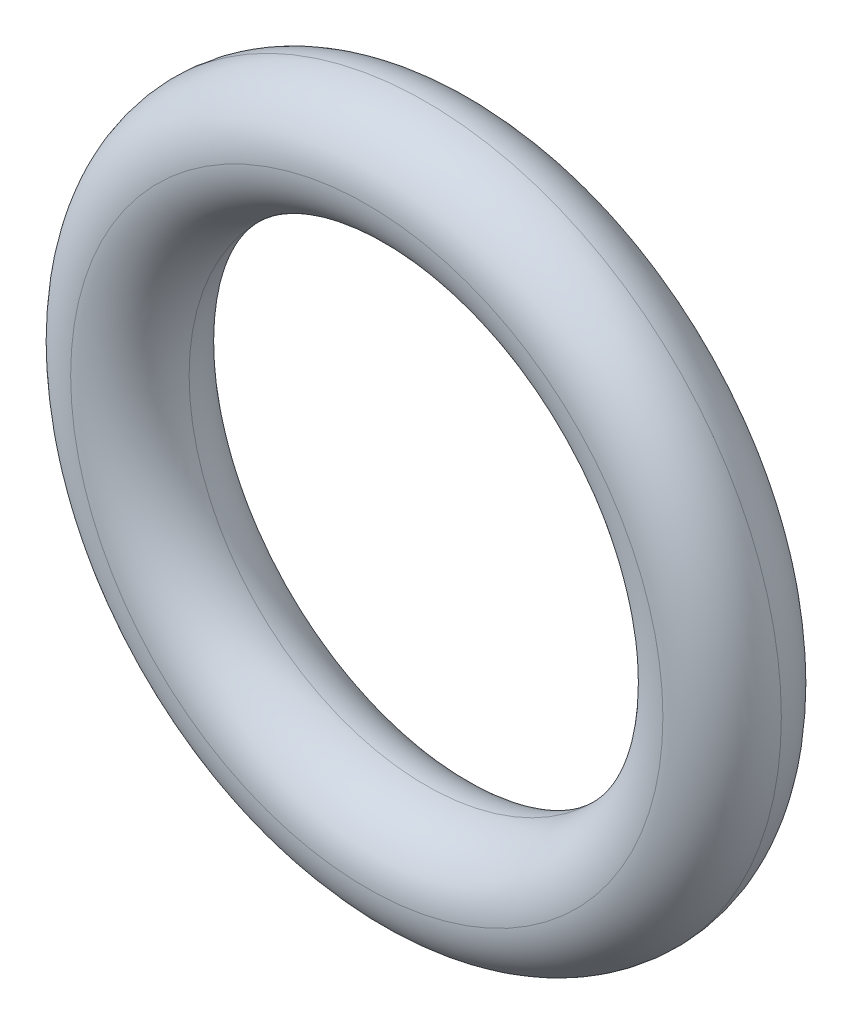
SolidWorks part; units mm, degrees
ref_plane "Front Plane" through (0, 0, 0) normal (0, 0, 1) x (1, 0, 0)
ref_plane "Top Plane" through (0, 0, 0) normal (0, 1, 0) x (1, 0, 0)
ref_plane "Right Plane" through (0, 0, 0) normal (1, 0, 0) x (0, 0, -1)
sketch "Sketch1" plane through (0, 0, 0) normal (0, 0, 1) x (1, 0, 0)
  circle A0 centre (0, 0) radius 76.2
  circle A1 centre (0, 0) radius 50.8
  dimension "D1" = 152.4
  dimension "D2" = 101.6
extrude "Boss-Extrude1" add sketch "Sketch1" along normal blind 25.4
fillet "Fillet1" radius 12.7 2 edges at (76.2, 0, 0) (76.2, 0, 25.4)
fillet "Fillet2" radius 12.7 2 edges at (50.8, 0, 25.4) (50.8, 0, 0)
